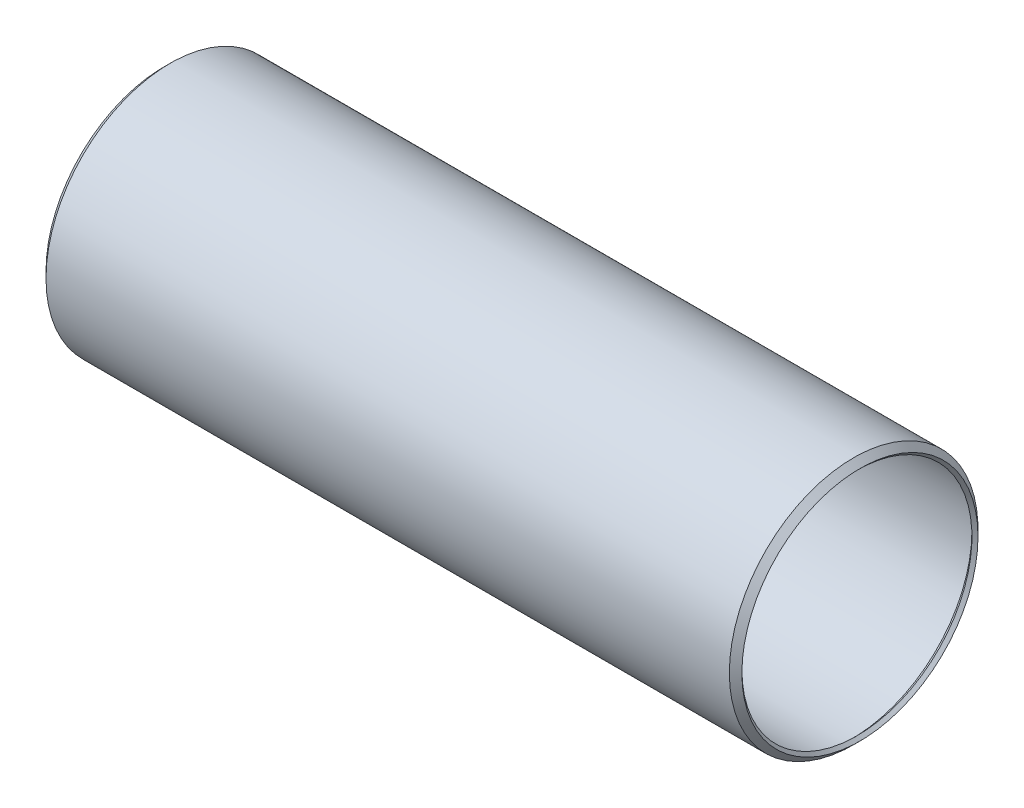
SolidWorks part; units mm, degrees
ref_plane "Front Plane" through (0, 0, 0) normal (0, 0, 1) x (1, 0, 0)
ref_plane "Top Plane" through (0, 0, 0) normal (0, 1, 0) x (1, 0, 0)
ref_plane "Right Plane" through (0, 0, 0) normal (1, 0, 0) x (0, 0, -1)
sketch "Sketch1" plane through (0, 0, 0) normal (0, 0, 1) x (1, 0, 0)
  line L0 (-139.1782, 25.1576) -> (-138.5316, 24.511)
  line L1 (-138.5316, 24.511) -> (-137.4648, 25.5778)
  line L2 (-137.4648, 25.5778) -> (7.3914, 25.5778)
  line L3 (7.3914, 25.5778) -> (8.4582, 24.511)
  line L4 (8.4582, 24.511) -> (9.1048, 25.1576)
  line L5 (9.1048, 25.1576) -> (7.7702, 26.4922)
  line L6 (7.7702, 26.4922) -> (-137.8436, 26.4922)
  line L7 (-137.8436, 26.4922) -> (-139.1782, 25.1576)
  line L8 (7.3914, 0) -> (-137.4648, 0) construction
revolve "Revolve1" add sketch "Sketch1" angle 360 about L8 reverse direction yes
ref_plane "Plane1" through (-76.7207, 0, 0) normal (1, 0, 0) x (0, 0, -1)
ref_plane "Plane2" through (42.8752, 0, 0) normal (1, 0, 0) x (0, 0, -1)
ref_plane "Plane3" through (-204.0128, 0, 0) normal (1, 0, 0) x (0, 0, -1)
ref_plane "Plane4" through (-130.0734, 0, 0) normal (1, 0, 0) x (0, 0, -1)
ref_plane "Plane5" through (0, 0, 0) normal (1, 0, 0) x (0, 0, -1)
ref_plane "Plane6" through (-204.0128, 0, 0) normal (1, 0, 0) x (0, 0, -1)
ref_plane "to_dummy XY" through (-130.0734, 0, 0) normal (-1, 0, 0) x (0, 0, 1)
ref_plane "to_dummy XZ" through (0, 0, 0) normal (0, 1, 0) x (1, 0, 0)
ref_plane "to_dummy YZ" through (0, 0, 0) normal (0, 0, -1) x (-1, 0, 0)
ref_axis "to_dummy X" through (-130.0734, 0, 80.9) along (0, 0, -1)
ref_axis "to_dummy Y" through (-130.0734, 50, 0) along (0, -1, 0)
ref_axis "to_dummy Z" through (-80.9, 0, 0) along (1, 0, 0)
sketch3d "to_dummy"
  point P0 (-130.0734, 0, 0)
ref_plane "to_dummy1 XY" through (-76.7207, 0, 0) normal (-1, 0, 0) x (0, 0, 1)
ref_plane "to_dummy1 XZ" through (0, 0, 0) normal (0, 1, 0) x (1, 0, 0)
ref_plane "to_dummy1 YZ" through (0, 0, 0) normal (0, 0, -1) x (-1, 0, 0)
ref_axis "to_dummy1 X" through (-76.7207, 0, 80.9) along (0, 0, -1)
ref_axis "to_dummy1 Y" through (-76.7207, 50, 0) along (0, -1, 0)
ref_axis "to_dummy1 Z" through (-80.9, 0, 0) along (1, 0, 0)
sketch3d "to_dummy1"
  point P0 (-76.7207, 0, 0)
ref_plane "to_front XY" through (-130.0734, 0, 0) normal (1, 0, 0) x (0, 0, -1)
ref_plane "to_front XZ" through (0, 0, 0) normal (0, -1, 0) x (-1, 0, 0)
ref_plane "to_front YZ" through (0, 0, 0) normal (0, 0, -1) x (-1, 0, 0)
ref_axis "to_front X" through (-130.0734, 0, 80.9) along (0, 0, -1)
ref_axis "to_front Y" through (-130.0734, -50, 0) along (0, 1, 0)
ref_axis "to_front Z" through (80.9, 0, 0) along (-1, 0, 0)
sketch3d "to_front"
  point P0 (-130.0734, 0, 0)
ref_plane "to_rear XY" through (0, 0, 0) normal (-1, 0, 0) x (0, 0, 1)
ref_plane "to_rear XZ" through (0, 0, 0) normal (0, 1, 0) x (1, 0, 0)
ref_plane "to_rear YZ" through (0, 0, 0) normal (0, 0, -1) x (-1, 0, 0)
ref_axis "to_rear X" through (0, 0, 80.9) along (0, 0, -1)
ref_axis "to_rear Y" through (0, 50, 0) along (0, -1, 0)
ref_axis "to_rear Z" through (-80.9, 0, 0) along (1, 0, 0)
sketch3d "to_rear"
  point P0 (0, 0, 0)
